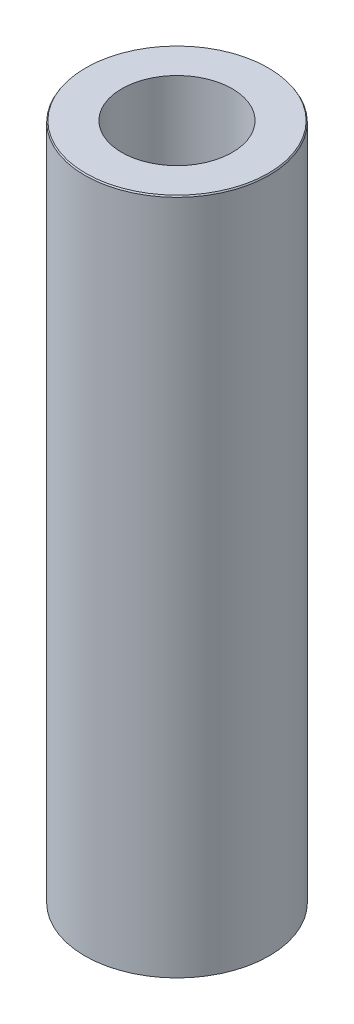
SolidWorks part; units mm, degrees
ref_plane "Front Plane" through (0, 0, 0) normal (0, 0, 1) x (1, 0, 0)
ref_plane "Top Plane" through (0, 0, 0) normal (0, 1, 0) x (1, 0, 0)
ref_plane "Right Plane" through (0, 0, 0) normal (1, 0, 0) x (0, 0, -1)
sketch "Sketch1" plane through (0, 0, 0) normal (0, 1, 0) x (1, 0, 0)
  circle A0 centre (0, 0) radius 52.5
  dimension "SHAFT_OD" = 105
extrude "Boss-Extrude1" add sketch "Sketch1" along normal blind 386.2652
sketch "Sketch2" plane through (0, 0, 0) normal (0, 1, 0) x (1, 0, 0)
  circle A0 centre (0, 0) radius 31.4577
  dimension "BORE_D" = 62.9155
extrude "Cut-Extrude1" cut sketch "Sketch2" along normal through all
chamfer "Chamfer1" distance 0.7743 angle 31.855 2 edges at (0, 386.2652, 52.5) (0, 0, 52.5) first distance on face at (0, 386.2652, 52.5) first distance on face at (0, 0, 31.4577)
